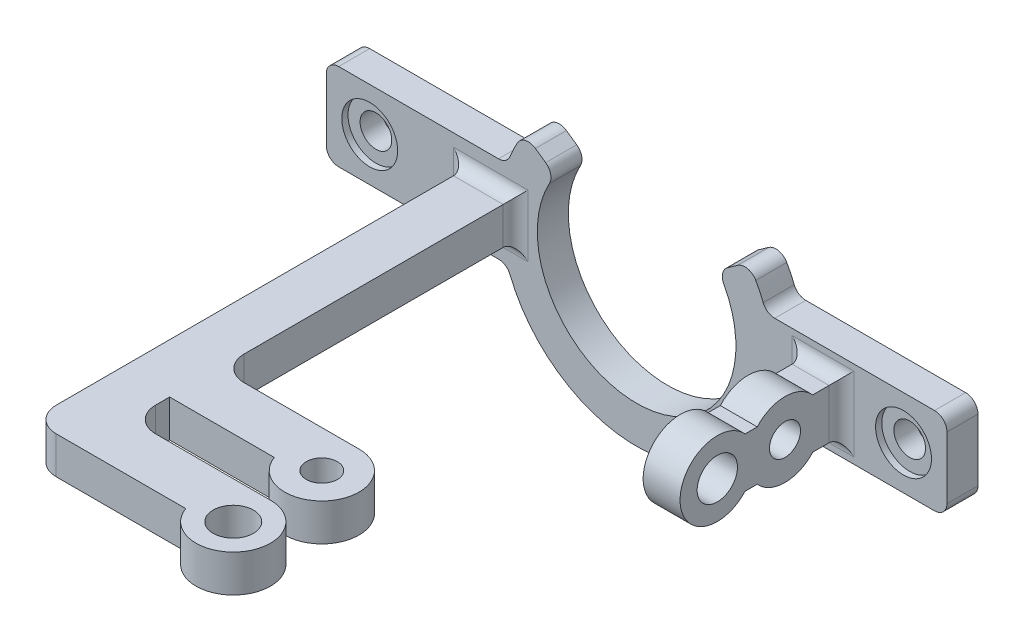
SolidWorks part; units mm, degrees
note: '?' marks a value the reader was unsure of.
ref_plane "Front Plane" through (0, 0, 0) normal (0, 0, 1) x (1, 0, 0)
ref_plane "Top Plane" through (0, 0, 0) normal (0, 1, 0) x (1, 0, 0)
ref_plane "Right Plane" through (0, 0, 0) normal (1, 0, 0) x (0, 0, -1)
sketch "Sketch1" plane through (0, 0, 0) normal (0, 0, 1) x (1, 0, 0)
  line L0 (100, 25) -> (100, 20)
  line L1 (100, 5) -> (100, 45) construction
  line L3 (98, 18) -> (72.2486, 18)
  line L4 (100, 25) -> (100, 30)
  line L5 (78.9438, 32) -> (98, 32)
  line L7 (78.9438, 32) -> (72.2486, 32)
  line L8 (54, 25) -> (106.793, 25) construction
  line L9 (50, 29) -> (50, 55.0668) construction
  line L16 (50, 25) -> (93.1322, 55.2015) construction
  line L17 (64.6534, 35.2604) -> (66.3009, 36.414)
  line L18 (50, 25) -> (6.8678, 55.2015) construction
  line L19 (46, 25) -> (-6.793, 25) construction
  line L20 (35.3466, 35.2604) -> (33.6991, 36.414)
  line L21 (21.0562, 32) -> (27.7514, 32)
  line L22 (2, 18) -> (27.7514, 18)
  line L23 (21.0562, 32) -> (2, 32)
  line L24 (0, 25) -> (0, 30)
  line L25 (0, 25) -> (0, 20)
  arc A0 (70.3945, 33.25) -> (69.1929, 35.7533) centre (50, 25) ccw
  arc A1 (35.955, 32.6641) -> (64.045, 32.6641) centre (50, 25) ccw
  arc A2 (29.6055, 16.75) -> (70.3945, 16.75) centre (50, 25) ccw
  circle A3 centre (93, 25) radius 2.55
  arc A14 (98, 32) -> (100, 30) centre (98, 30) cw
  arc A15 (98, 18) -> (100, 20) centre (98, 20) ccw
  arc A16 (72.2486, 18) -> (70.3945, 16.75) centre (72.2486, 16) ccw
  arc A17 (70.3945, 33.25) -> (72.2486, 32) centre (72.2486, 34) ccw
  arc A18 (64.6534, 35.2604) -> (64.045, 32.6641) centre (65.8006, 33.6221) ccw
  arc A19 (66.3009, 36.414) -> (69.1929, 35.7533) centre (67.4481, 34.7757) cw
  arc A21 (33.6991, 36.414) -> (30.8071, 35.7533) centre (32.5519, 34.7757) ccw
  arc A22 (35.3466, 35.2604) -> (35.955, 32.6641) centre (34.1994, 33.6221) cw
  arc A23 (29.6055, 33.25) -> (27.7514, 32) centre (27.7514, 34) cw
  arc A24 (27.7514, 18) -> (29.6055, 16.75) centre (27.7514, 16) cw
  arc A25 (2, 18) -> (0, 20) centre (2, 20) cw
  arc A26 (2, 32) -> (0, 30) centre (2, 30) ccw
  circle A27 centre (7, 25) radius 2.55
  arc A29 (29.6055, 33.25) -> (30.8071, 35.7533) centre (50, 25) cw
  point P30 (50, 3)
  point P31 (63.1064, 34.1772)
  point P35 (68.0213, 37.6187)
  point P39 (100, 32)
  point P73 (0, 32)
  point P74 (31.9787, 37.6187)
  point P75 (36.8936, 34.1772)
  dimension "D2" = 22
  dimension "D4" = 16
  dimension "D9" = 2
  dimension "D8" = 2
  dimension "D11" = 5.1
  dimension "D1" = 14
  dimension "D3" = 7
  dimension "D10" = 35
extrude "Boss-Extrude1" add sketch "Sketch1" along normal blind 5
fillet "Fillet2" [suppressed] radius 1
sketch "Sketch4" plane through (0, 0, 5) normal (0, 0, 1) x (1, 0, 0)
  circle A0 centre (93, 25) radius 4.5
  circle A1 centre (7, 25) radius 4.5
  dimension "D1" = 9
  dimension "D2" = 9
extrude "Cut-Extrude2" cut sketch "Sketch4" against normal blind 1
ref_axis "Axis1" through (93, 25, 4) along (0, 0, -1)?
ref_axis "Axis2" through (50, 25, 5) along (0, 0, -1)?
ref_plane "Plane1" through (0, 25, 0) normal (0, -1, 0) x (-1, 0, 0)
sketch "Sketch6" plane through (0, 25, 0) normal (0, -1, 0) x (-1, 0, 0)
  line L0 (-72.2486, -5) -> (-98, -5) construction
  line L1 (-77.0523, -5) -> (-83, -5)
  line L4 (-83, -5) -> (-83, -25)
  line L5 (-77.0523, -5) -> (-77.0523, -25)
  line L6 (-83, -25) -> (-77.0523, -25)
  line L7 (-93, -4) -> (-93, 0) construction
  dimension "D1" = 10
  dimension "D2" = 0
extrude "Boss-Extrude2" add sketch "Sketch6" along normal blind 4 and the other way blind 4
ref_plane "Plane2" through (77.0523, 21, 5) normal (1, 0, 0) x (0, 0, -1)
sketch "Sketch11" plane through (0, 0, 0) normal (0, 0, -1) x (-1, 0, 0)
  circle A0 centre (-93, 25) radius 4.5
  circle A1 centre (-7, 25) radius 4.5
  dimension "D1" = 9
  dimension "D2" = 9
extrude "Cut-Extrude3" cut sketch "Sketch11" against normal blind 0.5
thread "Thread1" [suppressed] pitch 0.8 start angle 0, offset 0, length 0, pitch 0.8, diameter 5.1
ref_plane "Plane3" through (90.45, 25, 4) normal (0, -1, 0) x (-1, 0, 0)
sketch "Thread Profile1" plane through (90.45, 25, 4) normal (0, -1, 0) x (-1, 0, 0)
  line L0 (0, 0) -> (0, 0.8) construction
  line L11 (0, 0) -> (0, 0.7)
  line L12 (0, 0.7) -> (-0.433, 0.45)
  line L13 (-0.433, 0.45) -> (-0.433, 0.25)
  line L15 (-0.433, 0.25) -> (0, 0)
  line L17 (-0.433, 0.35) -> (0, 0.35) construction
  point P2 (0, 0)
  dimension "Pitch" = 0.8
  dimension "Profile_Angle" = 60
  dimension "Profile_Land" = 0.2
  dimension "Profile_Height" = 0.433
sketch "Sketch16" plane through (0, 25, 0) normal (0, -1, 0) x (-1, 0, 0)
  line L0 (-27.7514, -5) -> (-2, -5) construction
  line L1 (-30.4943, -5) -> (-22.4943, -5)
  line L2 (-30.4943, -5) -> (-30.4943, -48.7321)
  line L3 (-30.4943, -75) -> (-26.4943, -75)
  line L4 (-22.4943, -5) -> (-22.4943, -71)
  line L5 (-30.4943, -60.7321) -> (-47.3614, -60.7321)
  line L6 (-30.4943, -75) -> (-47.3614, -75)
  line L8 (-34.4943, -67) -> (-53.0183, -67)
  line L10 (-53.0183, -52.7321) -> (-34.4943, -52.7321)
  line L11 (-30.4943, -60.7321) -> (-30.4943, -63)
  arc A0 (-53.0183, -67) -> (-47.3614, -75) centre (-53.0183, -73) ccw
  circle A1 centre (-53.0183, -73) radius 3.25
  arc A2 (-30.4943, -63) -> (-34.4943, -67) centre (-34.4943, -63) cw
  arc A3 (-26.4943, -75) -> (-22.4943, -71) centre (-26.4943, -71) ccw
  arc A4 (-53.0183, -52.7321) -> (-47.3614, -60.7321) centre (-53.0183, -58.7321) ccw
  circle A5 centre (-53.0183, -58.7321) radius 2.5
  arc A6 (-34.4943, -52.7321) -> (-30.4943, -48.7321) centre (-34.4943, -48.7321) ccw
  dimension "D5" = 6.5
  dimension "D6" = 4
  dimension "D7" = 4
  dimension "D8" = 12
  dimension "D10" = 5
  dimension "D11" = 4
  dimension "D1" = 0
  dimension "D2" = 70
  dimension "D3" = 8
  dimension "D4" = 6
  dimension "D9" = 8
extrude "Boss-Extrude3" add sketch "Sketch16" along normal blind 3 and the other way blind 3
fillet "Fillet3" radius 2 8 edges at (83, 25, 5) (80.0262, 29, 5) (77.0523, 25, 5) (80.0262, 21, 5) (26.4943, 22, 5) (30.4943, 25, 5) (22.4943, 25, 5) (26.4943, 28, 5)
sketch "Sketch17" plane through (83, 0, 0) normal (1, 0, 0) x (0, 0, -1)
  line L0 (-25, 29) -> (-25, 21) construction
  arc A0 (-19.5472, 27.5034) -> (-19.5472, 22.4966) centre (-25, 25) ccw
  arc A2 (-19.5472, 22.4966) -> (-19.5472, 27.5034) centre (-14.0944, 25) ccw
  dimension "D1" = 12
  dimension "D2" = 12
extrude "Boss-Extrude4" add sketch "Sketch17" against normal up to surface (5.9477 mm away) up to face at (77.0523, 25, 16)
sketch "Sketch18" plane through (83, 0, 0) normal (1, 0, 0) x (0, 0, -1)
  circle A0 centre (-25, 25) radius 3.25
  circle A1 centre (-14.0944, 25) radius 2.5
  dimension "D1" = 6.5
  dimension "D2" = 5
extrude "Cut-Extrude5" cut sketch "Sketch18" against normal up to next
thread "Thread2" [suppressed] pitch 0.8 start angle 0, offset 0, length 0, pitch 0.8, diameter 5.1
ref_plane "Plane4" through (4.45, 25, 4) normal (0, -1, 0) x (-1, 0, 0)
sketch "Thread Profile2" plane through (4.45, 25, 4) normal (0, -1, 0) x (-1, 0, 0)
  line L0 (0, 0) -> (0, 0.8) construction
  line L11 (0, 0) -> (0, 0.7)
  line L12 (0, 0.7) -> (-0.433, 0.45)
  line L13 (-0.433, 0.45) -> (-0.433, 0.25)
  line L15 (-0.433, 0.25) -> (0, 0)
  line L17 (-0.433, 0.35) -> (0, 0.35) construction
  point P2 (0, 0)
  dimension "Pitch" = 0.8
  dimension "Profile_Angle" = 60
  dimension "Profile_Land" = 0.2
  dimension "Profile_Height" = 0.433
equation "\"D3@Sketch1\"=\"D1@Sketch1\"/2"
